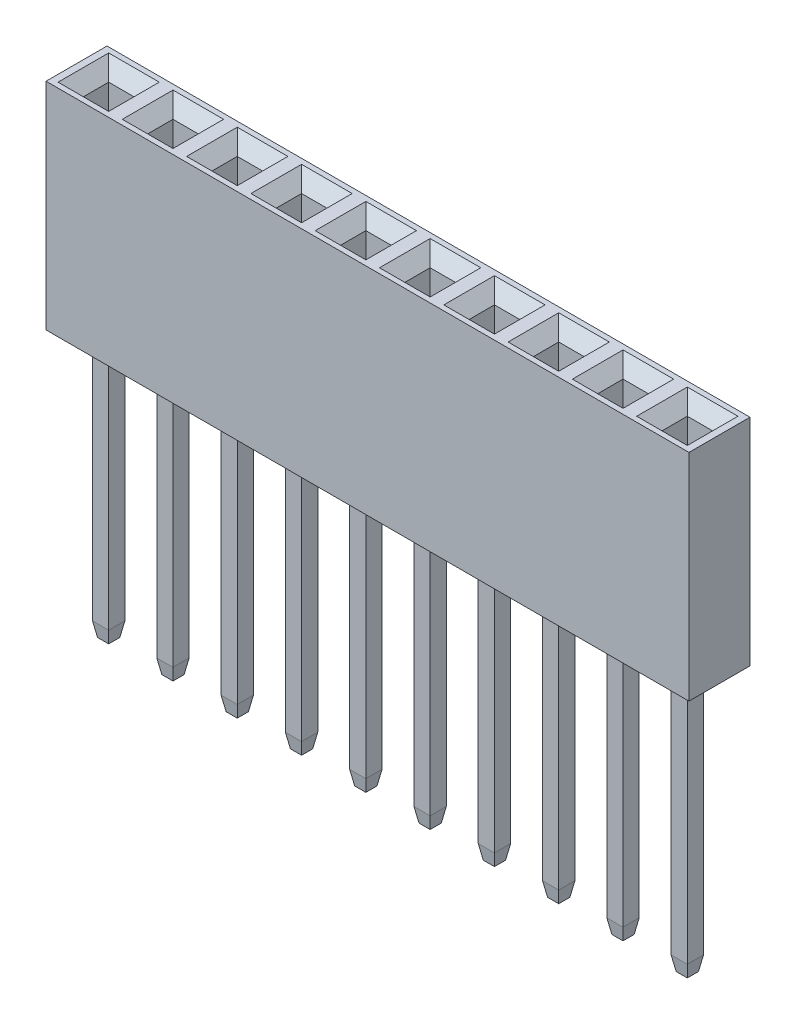
SolidWorks part; units mm, degrees
material "PA Type 6"
ref_plane "Front Plane" through (0, 0, 0) normal (0, 0, 1) x (1, 0, 0)
ref_plane "Top Plane" through (0, 0, 0) normal (0, 1, 0) x (1, 0, 0)
ref_plane "Right Plane" through (0, 0, 0) normal (1, 0, 0) x (0, 0, -1)
ref_plane "Plane1" through (0, -1.65, 0) normal (0, 1, 0) x (1, 0, 0)
sketch "Sketch2" plane through (0, 0, 0) normal (0, 1, 0) x (1, 0, 0)
  line L0 (0, -55) -> (0, 55) construction
  line L1 (-1.27, 1.205) -> (24.13, 1.205)
  line L2 (-1.27, 1.205) -> (-1.27, -1.205)
  line L3 (-1.27, -1.205) -> (24.13, -1.205)
  line L4 (24.13, 1.205) -> (24.13, -1.205)
  line L5 (-55, 0) -> (55, 0) construction
  dimension "D1" = 25.4
  dimension "D2" = 1.27
  dimension "D3" = 2.41
  dimension "D4" = 1.205
extrude "Boss-Extrude1" add sketch "Sketch2" along normal blind 8.51
sketch "Sketch5" plane through (0, 8.51, 0) normal (0, 1, 0) x (1, 0, 0)
  line L0 (-55, 0) -> (55, 0) construction
  line L1 (0.5, 0.5) -> (-0.5, 0.5)
  line L2 (0.5, 0.5) -> (0.5, -0.5)
  line L3 (0.5, -0.5) -> (-0.5, -0.5)
  line L4 (-0.5, 0.5) -> (-0.5, -0.5)
  line L5 (0, -55) -> (0, 55) construction
  dimension "D1" = 0.5
  dimension "D2" = 1
  dimension "D3" = 0.5
extrude "Cut-Extrude1" cut sketch "Sketch5" against normal blind 5
chamfer "Chamfer1" distance 0.5 angle 45 4 edges at (-0.5, 8.51, 0) (0, 8.51, 0.5) (0.5, 8.51, 0) (0, 8.51, -0.5)
pattern_linear "LPattern3" count 10 spacing 2.54 along (1, 0, 0) of "Chamfer1", "Cut-Extrude1"
ref_axis "Axis1" through (0, -11.44, 0) along (0, 1, 0)
sketch "Sketch11" plane through (0, 0, 0) normal (0, -1, 0) x (1, 0, 0)
  line L0 (0, 0) -> (2.54, 0) construction
  line L1 (-0.32, 0.32) -> (0.32, 0.32)
  line L2 (-0.32, 0.32) -> (-0.32, -0.32)
  line L3 (-0.32, -0.32) -> (0.32, -0.32)
  line L4 (0.32, 0.32) -> (0.32, -0.32)
  line L5 (-0.32, 0.32) -> (0.32, -0.32) construction
  line L6 (-0.32, -0.32) -> (0.32, 0.32) construction
  point P0 (0, 0)
  dimension "0.64" = 0.64
sketch "Sketch12" plane through (0, 0, 0) normal (0, 0, 1) x (1, 0, 0)
  line L0 (0, 8.51) -> (0, -10.49) construction
  line L1 (-1.27, 8.51) -> (24.13, 8.51) construction
  dimension "D1" = 19
extrude "Boss-Extrude2" add sketch "Sketch11" along normal blind 9.92
sketch "Sketch13" plane through (0, -9.92, 0) normal (0, -1, 0) x (1, 0, 0)
  line L4 (0.32, -0.32) -> (0.32, 0.32)
  line L5 (0.32, 0.32) -> (-0.32, 0.32)
  line L6 (-0.32, 0.32) -> (-0.32, -0.32)
  line L7 (-0.32, -0.32) -> (0.32, -0.32)
  line L8 (0.32, -0.32) -> (0.32, 0.32)
  line L9 (0.32, 0.32) -> (-0.32, 0.32)
  line L10 (-0.32, 0.32) -> (-0.32, -0.32)
  line L11 (-0.32, -0.32) -> (0.32, -0.32)
  dimension "D1" = 0
ref_plane "Plane2" through (0, -10.49, 0) normal (0, -1, 0) x (-1, 0, 0)
sketch "Sketch14" plane through (0, -10.49, 0) normal (0, -1, 0) x (-1, 0, 0)
  line L1 (-0.22, 0.22) -> (0.22, 0.22)
  line L2 (-0.22, 0.22) -> (-0.22, -0.22)
  line L3 (-0.22, -0.22) -> (0.22, -0.22)
  line L4 (0.22, 0.22) -> (0.22, -0.22)
  line L5 (-0.22, 0.22) -> (0.22, -0.22) construction
  line L6 (-0.22, -0.22) -> (0.22, 0.22) construction
  point P0 (0, 0)
  dimension "D1" = 0.44
loft "Loft1" add profiles "Sketch13", "Sketch14" connector at (-0.32, -9.92, 0.32) connector at (-0.22, -10.49, 0.22)
pattern_linear "LPattern4" count 10 spacing 2.54 along (1, 0, 0) of "Boss-Extrude2", "Loft1"
equation "\"D1@Sketch2\"=2.54 * 10"
